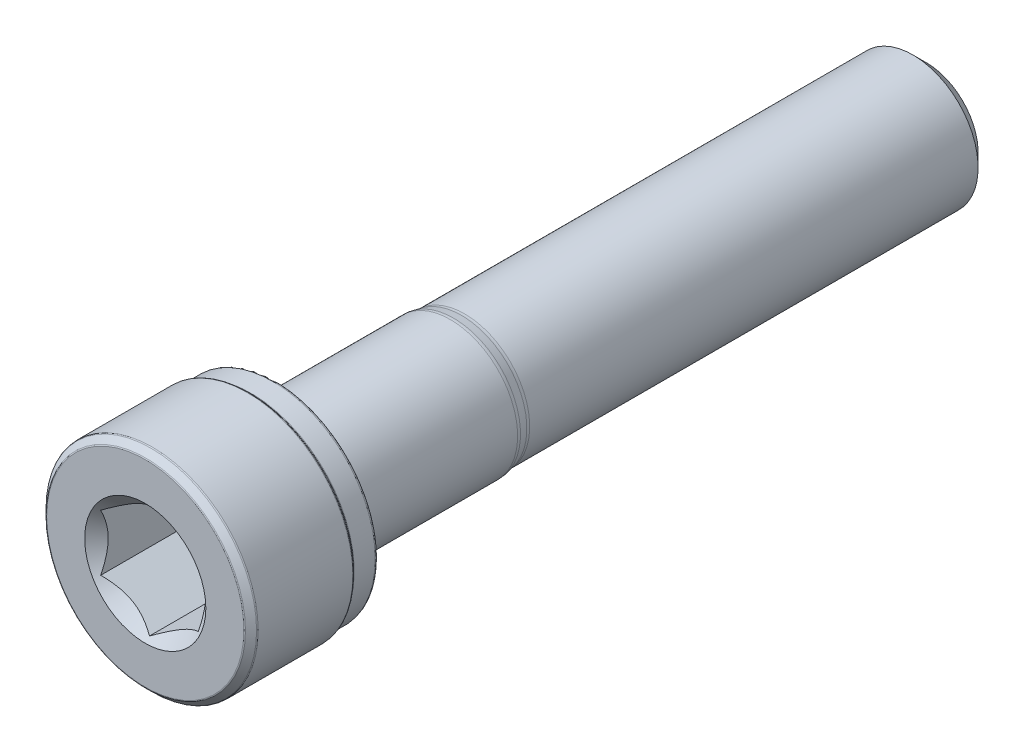
SolidWorks part; units mm, degrees
ref_plane "Front Plane" through (0, 0, 0) normal (0, 0, 1) x (1, 0, 0)
ref_plane "Top Plane" through (0, 0, 0) normal (0, 1, 0) x (1, 0, 0)
ref_plane "Right Plane" through (0, 0, 0) normal (1, 0, 0) x (0, 0, -1)
sketch "Sketch1" plane through (0, 0, 0) normal (1, 0, 0) x (0, 0, -1)
  line L0 (-24, 0) -> (24, 0) construction
  line L1 (24, 0) -> (24, 3.1881) construction
  line L2 (24, 3.1881) -> (23.1881, 4) construction
  line L3 (23.1881, 4) -> (23.0625, 4) construction
  line L4 (23.0625, 4) -> (-16, 4) construction
  line L5 (-16, 4) -> (-16, 6.5) construction
  line L6 (-16, 6.5) -> (-24, 6.5) construction
  line L7 (-24, 6.5) -> (-24, 0) construction
  line L8 (24, 3.1881) -> (24, 4) construction
  line L9 (23.9219, 4.1353) -> (24.5469, 3.0528) construction
  line L10 (24.5469, 3.0528) -> (25.1719, 4.1353) construction
  line L11 (25.1719, 4.1353) -> (23.9219, 4.1353) construction
  line L12 (24.5469, 4.1353) -> (24.5469, 4) construction
  line L13 (24.5469, 3.0528) -> (24.5469, 3.1881) construction
  line L14 (24.4688, 3.1881) -> (24.625, 3.1881) construction
  line L15 (24, 4) -> (25.0938, 4) construction
  line L16 (23.9609, 4.0677) -> (25.1328, 4.0677) construction
  line L17 (24, 0) -> (24, -4) construction
  line L18 (-16.4, 6.5) -> (-16, 6.1) construction
  line L19 (-23.6, 6.5) -> (-24, 6.1) construction
  line L20 (-16, 4) -> (-16, 0) construction
  line L21 (-16, 2) -> (-2.6667, 2) construction
  line L22 (-2.6667, 2) -> (10.6667, 2) construction
  line L23 (10.6667, 2) -> (24, 2) construction
  line L24 (-2.6667, 2) -> (-2.6667, 4) construction
  line L25 (-2.6667, 4) -> (-2.6667, 6.5) construction
  line L26 (10.6667, 2) -> (10.6667, 6.5) construction
  point P0 (-24, 3)
  point P3 (20.875, 4)
  point P4 (0, 0)
  point P18 (10.6667, 4)
  point P22 (24.5469, 3.1881)
  point P24 (23.0625, 4)
  point P25 (24.5469, 4)
  point P28 (24.5469, 4.0677)
  point P29 (20.875, -4)
  point P30 (-2.6667, 4)
  point P31 (-20, 6.5)
  point P37 (-17.4, 6.5)
  point P38 (-23.4, 6.5)
  point P45 (-2.6667, 2)
  point P46 (10.6667, 2)
  point P49 (-4, 4)
  dimension "D1" = 45
  dimension "D2" = 0.1562
  dimension "D7" = 0.4
  dimension "D8" = 0.4
  dimension "D9" = 0.4
  dimension "D10" = 0.2
  dimension "D11" = 1
  dimension "Drive Size" = 6
  dimension "Head Diameter" = 13
  dimension "Head Height" = 8
  dimension "Thread Pitch" = 1.25
  dimension "Thread Dia" = 8
  dimension "Length" = 40
  dimension "D12" = 0.9375
  dimension "D4" = 3.125
  dimension "Minimum Thread Length" = 28
sketch "Sketch2" plane through (0, 0, 0) normal (1, 0, 0) x (0, 0, -1)
  line L0 (-24, 0) -> (-24, 6.0586)
  line L1 (-23.5586, 6.5) -> (-17.7414, 6.5)
  line L2 (-16, 6.1375) -> (-16, 4.5353)
  line L4 (23.1881, 4) -> (24, 3.1881)
  line L5 (24, 3.1881) -> (24, 0)
  line L6 (-16, 6.5) -> (-24, 6.5) construction
  line L7 (24, 0) -> (-24, 0)
  line L8 (-23.6, 6.5) -> (-24, 6.1) construction
  line L10 (-23.6293, 6.4707) -> (-23.9707, 6.1293)
  line L12 (-17.4586, 6.3) -> (-16.1625, 6.3)
  line L14 (-16.4, 6.5) -> (-16, 6.1) construction
  line L15 (-17.6707, 6.4707) -> (-17.5293, 6.3293)
  line L17 (-16, 4) -> (-16, 6.5) construction
  line L18 (-15.6, 4.1353) -> (-5.2475, 4.1353)
  line L19 (-4.3703, 4) -> (23.1881, 4)
  line L20 (23.0625, 4) -> (-16, 4) construction
  line L21 (-5.0524, 4.1161) -> (-4.5653, 4.0192)
  line L22 (25.1719, 4.1353) -> (23.9219, 4.1353) construction
  arc A0 (-16.1625, 6.3) -> (-16, 6.1375) centre (-16.1625, 6.1375) cw
  arc A1 (-16, 4.5353) -> (-15.6, 4.1353) centre (-15.6, 4.5353) ccw
  arc A2 (-5.2475, 4.1353) -> (-5.0524, 4.1161) centre (-5.2475, 3.1353) cw
  arc A3 (-4.5653, 4.0192) -> (-4.3703, 4) centre (-4.3703, 5) ccw
  arc A4 (-23.6293, 6.4707) -> (-23.5586, 6.5) centre (-23.5586, 6.4) cw
  arc A5 (-23.9707, 6.1293) -> (-24, 6.0586) centre (-23.9, 6.0586) ccw
  arc A6 (-17.6707, 6.4707) -> (-17.7414, 6.5) centre (-17.7414, 6.4) ccw
  arc A7 (-17.5293, 6.3293) -> (-17.4586, 6.3) centre (-17.4586, 6.4) ccw
  point P22 (-16.2, 6.3)
  point P39 (-4.4688, 4)
  point P47 (-17.5, 6.3)
  dimension "D2" = 0.1625
  dimension "D3" = 0.4
  dimension "D6" = 1
  dimension "D7" = 0.1
  dimension "D1" = 1.5
  dimension "D4" = 11.25
  dimension "D5" = 0.4688
  dimension "D8" = 10.3525
revolve "Revolve1" add sketch "Sketch2" angle 360 about L7
sketch "Sketch3" plane through (0, 0, 24) normal (0, 0, 1) x (1, 0, 0)
  line L1 (3, -1.7321) -> (3, 1.7321)
  line L2 (3, 1.7321) -> (0, 3.4641)
  line L3 (0, 3.4641) -> (-3, 1.7321)
  line L4 (-3, 1.7321) -> (-3, -1.7321)
  line L5 (-3, -1.7321) -> (0, -3.4641)
  line L6 (0, -3.4641) -> (3, -1.7321)
  circle A0 centre (0, 0) radius 3 construction
  circle A1 centre (0, 0) radius 6.5 construction
  circle A2 centre (0, 0) radius 6.5 construction
  circle A3 centre (0, 0) radius 3.4641 construction
  dimension "D1" = 6.9282
extrude "Cut-Extrude1" cut sketch "Sketch3" against normal offset from surface (7 mm away) 1 up to face at (-6.1375, 0, 16)
sketch "Sketch4" plane through (0, 0, 24) normal (0, 0, 1) x (1, 0, 0)
  circle A0 centre (0, 0) radius 3.7239
  dimension "D1" = 7.4478
extrude "Cut-Extrude2" cut sketch "Sketch4" against normal up to vertex (4 mm away) draft 45 up to point (0, 6.5, 20)
sketch "Sketch11" plane through (0, 0, 0) normal (1, 0, 0) x (0, 0, -1)
  line L0 (-24, 0) -> (24, 0) construction
  line L1 (-24, 0) -> (24, 0) construction
  line L2 (-7.1886, -4) -> (-7.1886, 4) construction
  line L3 (23.0625, 4) -> (-16, 4) construction
  line L4 (-13.4119, -4) -> (-13.4119, 4) construction
  line L5 (-5.2475, 4.1353) -> (-5.2475, -4.1353) construction
  point P7 (-7.1886, 0)
  point P10 (-13.4119, 0)
  dimension "D1" = 2.5881
  dimension "D2" = 1.9411
sketch "Sketch6" [suppressed] plane through (0, 0, -24) normal (0, 0, -1) x (-1, 0, 0)
  circle A0 centre (0, 0) radius 4
curve "Helix/Spiral1" [suppressed] pitch 1.25 height 29.25 turns 23.4
sketch "Sketch10" [suppressed] plane through (0, 0, 0) normal (1, 0, 0) x (0, 0, -1)
  line L0 (-4, -4) -> (-4, 4)
  line L2 (-24, 0) -> (24, 0) construction
  point P3 (-4, 0)
split "Split1" [suppressed] bodies to split 106
sketch "Sketch7" [suppressed] plane through (0, 0, 0) normal (1, 0, 0) x (0, 0, -1)
  line L0 (23.9609, 4.0677) -> (25.1328, 4.0677)
  line L1 (25.1328, 4.0677) -> (24.625, 3.1881)
  line L2 (24.625, 3.1881) -> (24.4688, 3.1881)
  line L3 (24.4688, 3.1881) -> (23.9609, 4.0677)
sweep "Cut-Sweep1" [suppressed] cut profiles "Sketch7" path "Helix/Spiral1"
sketch "Sketch8" [suppressed] plane through (0, 0, 0) normal (1, 0, 0) x (0, 0, -1)
  line L0 (-16, 0) -> (-16, 4)
  line L2 (-16, 4) -> (-4, 4)
  line L4 (-4, 4) -> (-1.6906, 0)
  line L5 (-1.6906, 0) -> (-16, 0)
  line L6 (23.0625, 4) -> (-16, 4) construction
  line L7 (-24, 0) -> (24, 0) construction
  dimension "D1" = 60
  dimension "D2" = 28
revolve "Revolve2" [suppressed] add sketch "Sketch8" angle 360 about L5
sketch "Sketch9" [suppressed] plane through (0, 0, 24) normal (0, 0, 1) x (1, 0, 0)
  line L0 (-0.0297, 6.3662) -> (-0.1625, 6.6628)
  line L1 (-0.1625, 6.6628) -> (0.1625, 6.6628)
  line L2 (0.1625, 6.6628) -> (0.0297, 6.3662)
  line L3 (0, 6.5) -> (0, 6.1) construction
  line L4 (0, 0) -> (-0.1625, 6.6628) construction
  line L5 (0.1625, 6.6628) -> (0, 0) construction
  circle A0 centre (0, 0) radius 6.3 construction
  arc A4 (-0.0297, 6.3662) -> (0.0297, 6.3662) centre (0, 6.3795) ccw
  point P10 (0, 6.3)
  point P19 (0, 6.3)
  dimension "D2" = 0.0325
  dimension "D1" = 0.325
  dimension "D3" = 2.794
extrude "Cut-Extrude3" [suppressed] cut sketch "Sketch9" against normal through all
pattern_circular "CirPattern1" [suppressed] count 80 over 360 of bodies 112
equation "\"D2@Sketch1\" = \"Thread Pitch@Sketch1\" / 8"
equation "\"D4@Helix/Spiral1\" = \"Thread Pitch@Sketch1\""
equation "\"D7@Sketch1\" = \"Head Height@Sketch1\" * .05"
equation "\"D8@Sketch1\"=\"D7@Sketch1\""
equation "\"D9@Sketch1\"=\"D7@Sketch1\""
equation "\"D10@Sketch1\"=\"D7@Sketch1\"/2"
equation "\"D11@Sketch1\"=\"D10@Sketch1\"*5"
equation "\"D4@Sketch1\"=\"Thread Pitch@Sketch1\"*2.5"
equation "\"D12@Sketch1\"=\"Thread Pitch@Sketch1\"*.75"
equation "\"D3@Helix/Spiral1\"=\"Minimum Thread Length@Sketch1\"+\"Thread Pitch@Sketch1\""
equation "\"D2@Sketch8\"=\"Minimum Thread Length@Sketch1\""
equation "\"D1@Sketch2\"=\"Head Height@Sketch1\"*0.1875"
equation "\"D2@Sketch2\"=\"Head Diameter@Sketch1\"*0.0125"
equation "\"D3@Sketch2\"=\"Thread Dia@Sketch1\"*0.05"
equation "\"D1@Sketch9\"=\"Head Diameter@Sketch1\"*0.025"
equation "\"D2@Sketch9\"=\"D1@Sketch9\"*0.1"
equation "\"D1@CirPattern1\"=int ((360/\"D3@Sketch9\")*0.625)"
equation "\"D5@Sketch2\"=\"D12@Sketch1\"*0.5"
equation "\"D6@Sketch2\"=\"Thread Dia@Sketch1\"*0.125"
equation "\"D7@Sketch2\"=\"D8@Sketch1\"*0.25"
equation "\"D1@Sketch11\"=\"D8@Sketch2\"*0.25"
equation "\"D2@Sketch11\"=\"D8@Sketch2\"*0.1875"
equation "\"D1@Sketch4\"=\"D1@Sketch3\"*1.075"
